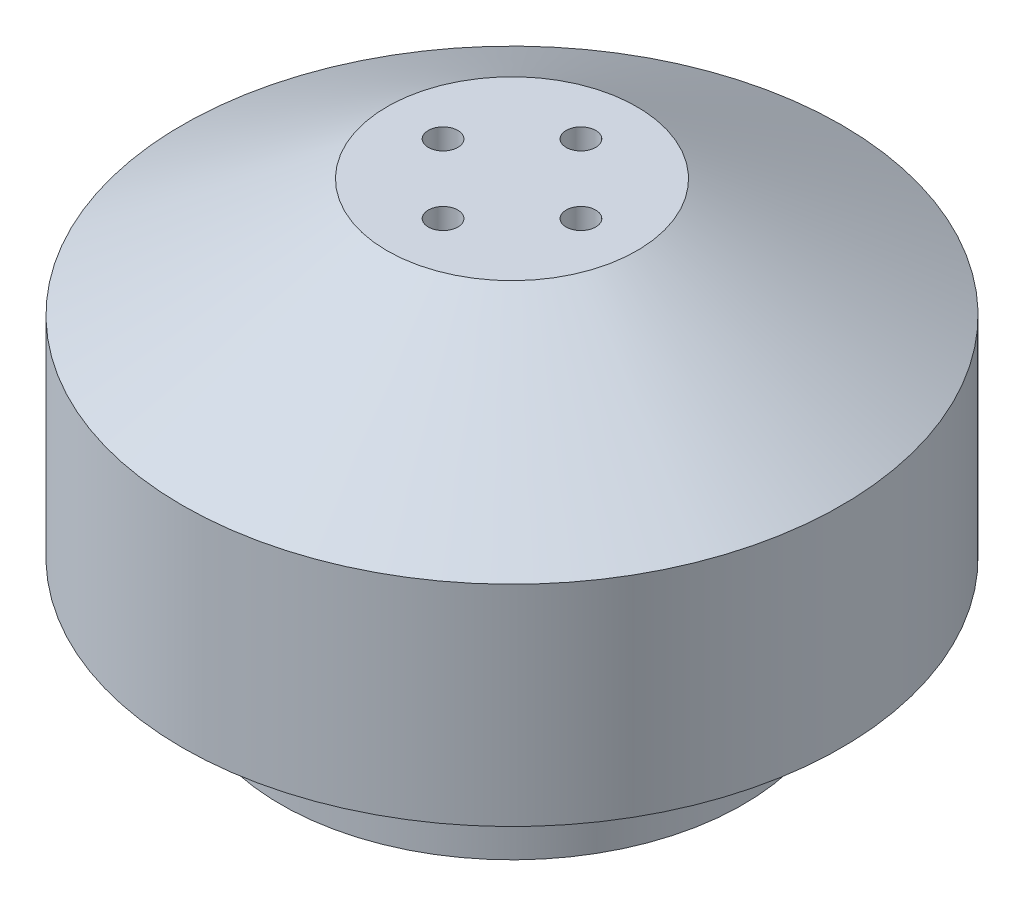
SolidWorks part; units mm, degrees
ref_plane "Front Plane" through (0, 0, 0) normal (0, 0, 1) x (1, 0, 0)
ref_plane "Top Plane" through (0, 0, 0) normal (0, 1, 0) x (1, 0, 0)
ref_plane "Right Plane" through (0, 0, 0) normal (1, 0, 0) x (0, 0, -1)
sketch "Sketch1" plane through (0, 0, 0) normal (0, 1, 0) x (1, 0, 0)
  circle A0 centre (0, 0) radius 21.25
  dimension "D1" = 42.5
extrude "Boss-Extrude1" add sketch "Sketch1" along normal blind 27.5
sketch "Sketch2" plane through (0, 0, 0) normal (0, -1, 0) x (1, 0, 0)
  circle A0 centre (0, 0) radius 14.9
  circle A2 centre (0, 0) radius 21.25
  circle A3 centre (0, 0) radius 21.25
  dimension "D1" = 0
  dimension "D2" = 6.35
extrude "Cut-Extrude1" cut sketch "Sketch2" against normal blind 6.35
chamfer "Chamfer1" distance 7.62 angle 60 1 edges at (0, 27.5, 21.25) first distance on face at (0, 27.5, 21.25)
sketch "Sketch3" plane through (0, 27.5, 0) normal (0, 1, 0) x (1, 0, 0)
  circle A0 centre (0, 4.445) radius 0.9525
  circle A1 centre (4.445, 0) radius 0.9525
  circle A2 centre (0, -4.445) radius 0.9525
  circle A3 centre (-4.445, 0) radius 0.9525
  point P2 (-1.1449, -5.057)
  point P4 (0, 0)
  point P12 (0, 0)
  dimension "D1" = 4.445
  dimension "D2" = 1.905
  dimension "D3" = 4
extrude "Cut-Extrude2" cut sketch "Sketch3" against normal blind 6.35
